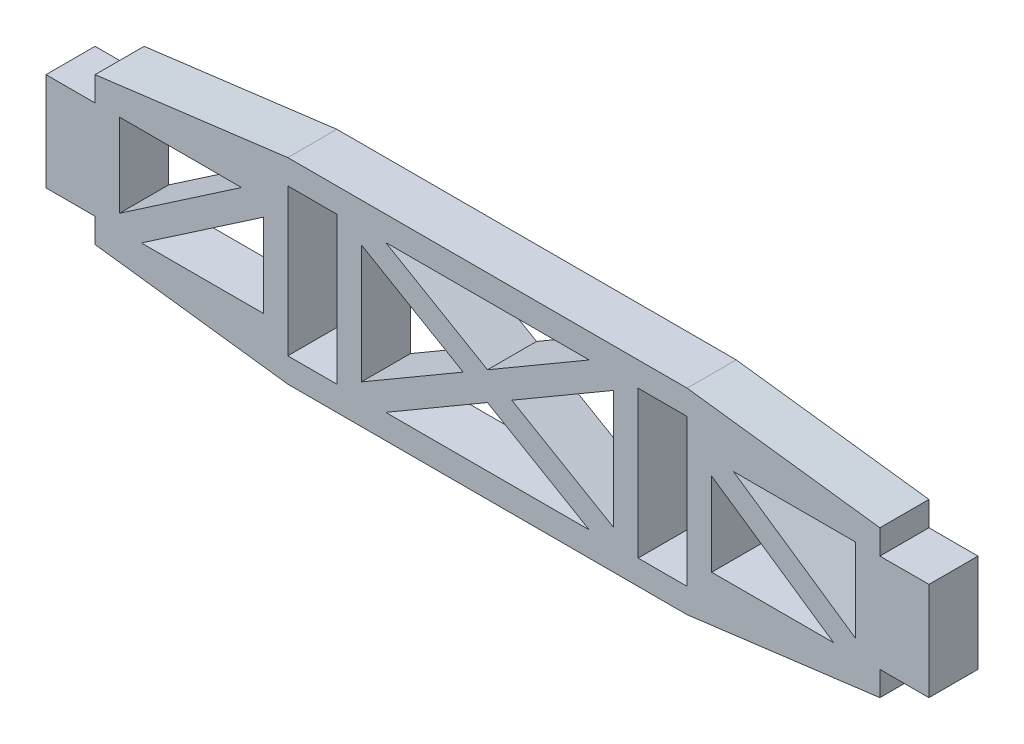
SolidWorks part; units mm, degrees
ref_plane "Front Plane" through (0, 0, 0) normal (0, 0, 1) x (1, 0, 0)
ref_plane "Top Plane" through (0, 0, 0) normal (0, 1, 0) x (1, 0, 0)
ref_plane "Right Plane" through (0, 0, 0) normal (1, 0, 0) x (0, 0, -1)
sketch "Sketch1" plane through (0, 0, 0) normal (0, 0, 1) x (1, 0, 0)
  line L0 (-50.8, -6.35) -> (-50.8, 6.35) construction
  line L1 (-50.8, -9.525) -> (50.8, -9.525) construction
  line L2 (-50.8, -9.525) -> (-50.8, -6.35)
  line L3 (-50.8, 9.525) -> (50.8, 9.525) construction
  line L4 (50.8, -9.525) -> (50.8, -6.35)
  line L5 (-50.8, -9.525) -> (50.8, 9.525) construction
  line L6 (-50.8, 9.525) -> (50.8, -9.525) construction
  line L7 (-50.8, 6.35) -> (-57.15, 6.35)
  line L8 (-50.8, 6.35) -> (-50.8, -6.35) construction
  line L9 (-50.8, -6.35) -> (-57.15, -6.35)
  line L10 (-57.15, 6.35) -> (-57.15, -6.35)
  line L11 (50.8, 6.35) -> (57.15, 6.35)
  line L12 (50.8, 6.35) -> (50.8, -6.35) construction
  line L13 (50.8, -6.35) -> (57.15, -6.35)
  line L14 (57.15, 6.35) -> (57.15, -6.35)
  line L15 (-50.8, 6.35) -> (-50.8, 9.525)
  line L16 (50.8, -6.35) -> (50.8, 6.35) construction
  line L17 (50.8, 6.35) -> (50.8, 9.525)
  line L18 (0, -55) -> (0, 55) construction
  line L19 (-25.85, 9.525) -> (-19.5, 9.525)
  line L20 (-25.85, 9.525) -> (-25.85, -9.525)
  line L21 (-25.85, -9.525) -> (-19.5, -9.525)
  line L22 (-19.5, 9.525) -> (-19.5, -9.525)
  line L23 (25.85, -9.525) -> (19.5, -9.525)
  line L24 (19.5, 9.525) -> (19.5, -9.525)
  line L25 (25.85, 9.525) -> (19.5, 9.525)
  line L26 (25.85, 9.525) -> (25.85, -9.525)
  line L27 (-50.8, 9.525) -> (-25.85, 12.7)
  line L28 (-25.85, 12.7) -> (25.85, 12.7)
  line L29 (25.85, 12.7) -> (50.8, 9.525)
  line L30 (50.8, -9.525) -> (25.85, -12.7)
  line L31 (25.85, -12.7) -> (-25.85, -12.7)
  line L32 (-25.85, -12.7) -> (-50.8, -9.525)
  point P0 (0, 0)
  point P15 (57.15, 0)
  point P16 (-57.15, 0)
  point P26 (-25.85, 0)
  point P32 (0, 0)
  point P33 (0, 0)
  point P36 (0, 0)
  dimension "D1" = 101.6
  dimension "D2" = 6.35
  dimension "D3" = 12.7
  dimension "D4" = 3.175
  dimension "D5" = 39
  dimension "D6" = 19.05
  dimension "D7" = 3.175
extrude "Boss-Extrude1" add sketch "Sketch1" along normal mid plane 6.35
sketch "Sketch2" plane through (0, 0, 3.175) normal (0, 0, 1) x (1, 0, 0)
  line L0 (-1000, 0) -> (49000, 0) construction
  line L1 (-47.625, 6.35) -> (-47.625, -6.35)
  line L2 (-47.625, -6.35) -> (-29.025, -6.35)
  line L3 (-29.025, -6.35) -> (-29.025, 6.35)
  line L4 (-29.025, 6.35) -> (-47.625, 6.35)
  line L5 (-50.8, 6.35) -> (-57.15, 6.35) construction
  line L6 (-50.8, 9.525) -> (-50.8, 6.35) construction
  line L7 (-31.8403, 6.35) -> (-47.625, -4.4277)
  line L8 (-50.8, 6.35) -> (-47.625, 6.35) construction
  line L9 (16.325, -9.525) -> (-16.325, -9.525)
  line L10 (16.325, -9.525) -> (16.325, 9.525)
  line L11 (16.325, 9.525) -> (-16.325, 9.525)
  line L12 (-16.325, -9.525) -> (-16.325, 9.525)
  line L13 (16.325, -9.525) -> (-16.325, 9.525) construction
  line L14 (16.325, 9.525) -> (-16.325, -9.525) construction
  line L15 (-29.025, 6.35) -> (-25.85, 6.35) construction
  line L16 (-19.5, 9.525) -> (-16.325, 9.525) construction
  line L17 (16.325, 9.525) -> (19.5, 9.525) construction
  line L18 (-47.625, 6.35) -> (-29.025, -6.35) construction
  line L19 (-29.025, 6.35) -> (-47.625, -6.35) construction
  line L20 (-29.025, 4.4277) -> (-44.8097, -6.35)
  line L21 (-29.9202, 7.661) -> (-48.5202, -5.039) construction
  line L22 (-28.1298, 5.039) -> (-46.7298, -7.661) construction
  line L23 (16.325, -7.687) -> (-13.1749, 9.525)
  line L24 (13.1749, 9.525) -> (-16.325, -7.687)
  line L25 (13.1749, -9.525) -> (-16.325, 7.687)
  line L26 (16.325, 7.687) -> (-13.1749, -9.525)
  line L27 (17.125, -8.1538) -> (-15.525, 10.8962) construction
  line L28 (15.525, -10.8962) -> (-17.125, 8.1538) construction
  line L29 (15.525, 10.8962) -> (-17.125, -8.1538) construction
  line L30 (17.125, 8.1538) -> (-15.525, -10.8962) construction
  line L31 (0, -3.4925) -> (0, 3.4925) construction
  line L32 (31.8403, 6.35) -> (47.625, -4.4277)
  line L33 (29.025, 4.4277) -> (44.8097, -6.35)
  line L34 (29.025, -6.35) -> (29.025, 6.35)
  line L35 (47.625, -6.35) -> (29.025, -6.35)
  line L36 (47.625, 6.35) -> (47.625, -6.35)
  line L37 (29.025, 6.35) -> (47.625, 6.35)
  line L38 (-19.5, -9.525) -> (-19.5, 9.525) construction
  line L39 (-25.85, 9.525) -> (-25.85, -9.525) construction
  point P9 (-47.625, 0)
  point P14 (0, 0)
  point P59 (14.6982, 6.35)
  point P60 (0, 0)
  point P63 (-27.1073, 6.35)
  point P66 (-16.325, -6.35)
  point P67 (0, 0)
  dimension "D1" = 3.175
  dimension "D2" = 1.5875
  dimension "D6" = 19.05
  dimension "D3" = 1.5875
  dimension "D4" = 1.5875
  dimension "D5" = 1.5875
extrude "Cut-Extrude1" cut sketch "Sketch2" against normal through all contours L7 L4 L1 | L3 L20 L2 | L24 L25 L12 | L24 L11 L23 | L10 L26 L23 | L25 L26 L9 | L35 L33 L34 | L37 L32 L36 region at (-42.3634, 2.7574, 3.175) region at (-34.2866, -2.7574, 3.175) region at (0, -6.9627, 3.175) region at (11.9334, 0, 3.175) region at (-11.9334, 0, 3.175) region at (0, 6.9627, 3.175) region at (42.3634, 2.7574, 3.175) region at (34.2866, -2.7574, 3.175)
